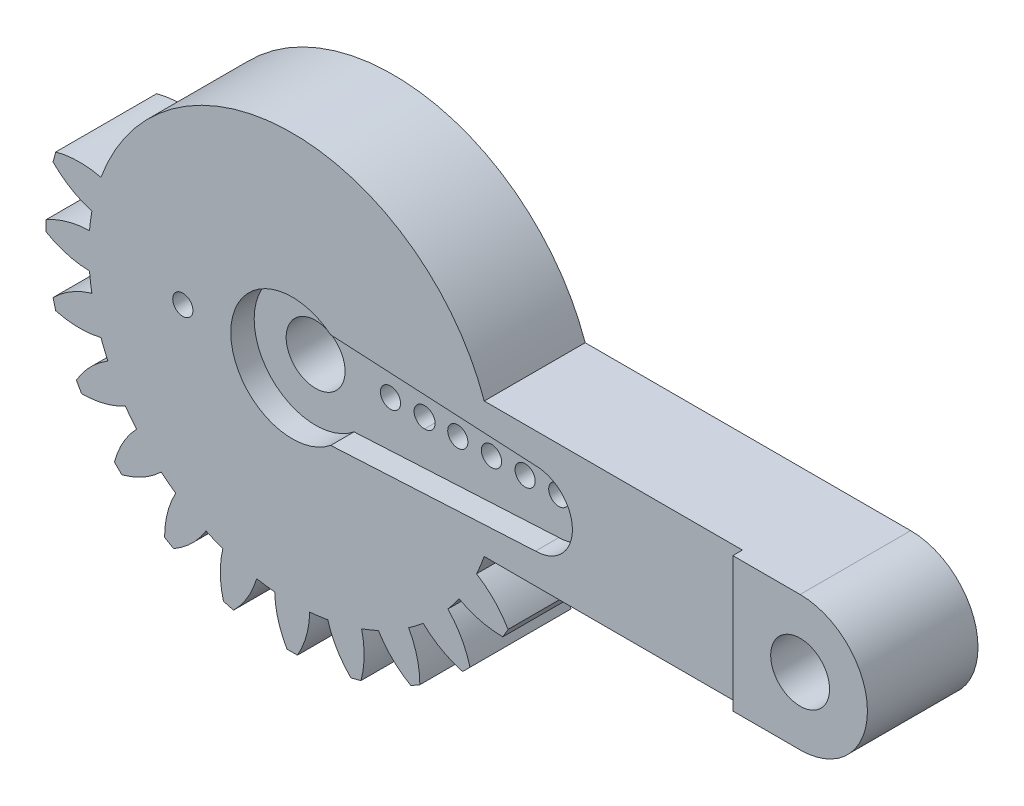
SolidWorks part; units mm, degrees
ref_plane "Front Plane" through (0, 0, 0) normal (0, 0, 1) x (1, 0, 0)
ref_plane "Top Plane" through (0, 0, 0) normal (0, 1, 0) x (1, 0, 0)
ref_plane "Right Plane" through (0, 0, 0) normal (1, 0, 0) x (0, 0, -1)
sketch "Sketch2" plane through (0, 0, 0) normal (0, 0, 1) x (1, 0, 0)
  line L0 (0, 0) -> (30.75, 0) construction
  line L1 (0, -14.63) -> (0, 14.63) construction
  line L2 (-0.31, 14.63) -> (0.31, 14.63)
  line L3 (3.4871, 14.2117) -> (4.086, 14.0513)
  line L4 (7.0465, 12.825) -> (7.5835, 12.515)
  line L5 (10.1258, 10.5642) -> (10.5642, 10.1258)
  line L6 (12.515, 7.5835) -> (12.825, 7.0465)
  line L7 (14.0513, 4.086) -> (14.2117, 3.4871)
  line L8 (14.63, 0.31) -> (14.63, -0.31)
  line L9 (14.2117, -3.4871) -> (14.0513, -4.086)
  line L10 (12.825, -7.0465) -> (12.515, -7.5835)
  line L11 (10.5642, -10.1258) -> (10.1258, -10.5642)
  line L12 (7.5835, -12.515) -> (7.0465, -12.825)
  line L13 (4.086, -14.0513) -> (3.4871, -14.2117)
  line L14 (0.31, -14.63) -> (-0.31, -14.63)
  line L15 (-3.4871, -14.2117) -> (-4.086, -14.0513)
  line L16 (-7.0465, -12.825) -> (-7.5835, -12.515)
  line L17 (-10.1258, -10.5642) -> (-10.5642, -10.1258)
  line L18 (-12.515, -7.5835) -> (-12.825, -7.0465)
  line L19 (-14.0513, -4.086) -> (-14.2117, -3.4871)
  line L20 (-14.63, -0.31) -> (-14.63, 0.31)
  line L21 (-14.2117, 3.4871) -> (-14.0513, 4.086)
  line L22 (-12.825, 7.0465) -> (-12.515, 7.5835)
  line L23 (-10.5642, 10.1258) -> (-10.1258, 10.5642)
  line L24 (-7.5835, 12.515) -> (-7.0465, 12.825)
  line L25 (-4.086, 14.0513) -> (-3.4871, 14.2117)
  line L26 (30.75, -4) -> (30.75, 4) construction
  line L27 (30.75, 4) -> (11.4091, 4)
  line L28 (30.75, -4) -> (11.4091, -4)
  circle A0 centre (0, 0) radius 1.75
  circle A1 centre (0, 0) radius 12.09
  circle A2 centre (30.75, 0) radius 1.75
  arc A3 (-1.04, 12.0452) -> (-0.31, 14.63) centre (4.3585, 11.9161) cw
  arc A4 (1.04, 12.0452) -> (0.31, 14.63) centre (-4.3585, 11.9161) ccw
  arc A5 (4.1221, 11.3656) -> (4.086, 14.0513) centre (-1.1258, 12.6381) ccw
  arc A6 (2.113, 11.9039) -> (3.4871, 14.2117) centre (7.294, 10.382) cw
  arc A7 (6.9233, 9.9114) -> (7.5835, 12.515) centre (2.1835, 12.4988) ccw
  arc A8 (5.1219, 10.9514) -> (7.0465, 12.825) centre (9.7326, 8.1404) cw
  arc A9 (9.2526, 7.7818) -> (10.5642, 10.1258) centre (5.344, 11.5078) ccw
  arc A10 (7.7818, 9.2526) -> (10.1258, 10.5642) centre (11.5078, 5.344) cw
  arc A11 (10.9514, 5.1219) -> (12.825, 7.0465) centre (8.1404, 9.7326) ccw
  arc A12 (9.9114, 6.9233) -> (12.515, 7.5835) centre (12.4988, 2.1835) cw
  arc A13 (11.9039, 2.113) -> (14.2117, 3.4871) centre (10.382, 7.294) ccw
  arc A14 (11.3656, 4.1221) -> (14.0513, 4.086) centre (12.6381, -1.1258) cw
  arc A15 (12.0452, -1.04) -> (14.63, -0.31) centre (11.9161, 4.3585) ccw
  arc A16 (12.0452, 1.04) -> (14.63, 0.31) centre (11.9161, -4.3585) cw
  arc A17 (11.3656, -4.1221) -> (14.0513, -4.086) centre (12.6381, 1.1258) ccw
  arc A18 (11.9039, -2.113) -> (14.2117, -3.4871) centre (10.382, -7.294) cw
  arc A19 (9.9114, -6.9233) -> (12.515, -7.5835) centre (12.4988, -2.1835) ccw
  arc A20 (10.9514, -5.1219) -> (12.825, -7.0465) centre (8.1404, -9.7326) cw
  arc A21 (7.7818, -9.2526) -> (10.1258, -10.5642) centre (11.5078, -5.344) ccw
  arc A22 (9.2526, -7.7818) -> (10.5642, -10.1258) centre (5.344, -11.5078) cw
  arc A23 (5.1219, -10.9514) -> (7.0465, -12.825) centre (9.7326, -8.1404) ccw
  arc A24 (6.9233, -9.9114) -> (7.5835, -12.515) centre (2.1835, -12.4988) cw
  arc A25 (2.113, -11.9039) -> (3.4871, -14.2117) centre (7.294, -10.382) ccw
  arc A26 (4.1221, -11.3656) -> (4.086, -14.0513) centre (-1.1258, -12.6381) cw
  arc A27 (-1.04, -12.0452) -> (-0.31, -14.63) centre (4.3585, -11.9161) ccw
  arc A28 (1.04, -12.0452) -> (0.31, -14.63) centre (-4.3585, -11.9161) cw
  arc A29 (-4.1221, -11.3656) -> (-4.086, -14.0513) centre (1.1258, -12.6381) ccw
  arc A30 (-2.113, -11.9039) -> (-3.4871, -14.2117) centre (-7.294, -10.382) cw
  arc A31 (-6.9233, -9.9114) -> (-7.5835, -12.515) centre (-2.1835, -12.4988) ccw
  arc A32 (-5.1219, -10.9514) -> (-7.0465, -12.825) centre (-9.7326, -8.1404) cw
  arc A33 (-9.2526, -7.7818) -> (-10.5642, -10.1258) centre (-5.344, -11.5078) ccw
  arc A34 (-7.7818, -9.2526) -> (-10.1258, -10.5642) centre (-11.5078, -5.344) cw
  arc A35 (-10.9514, -5.1219) -> (-12.825, -7.0465) centre (-8.1404, -9.7326) ccw
  arc A36 (-9.9114, -6.9233) -> (-12.515, -7.5835) centre (-12.4988, -2.1835) cw
  arc A37 (-11.9039, -2.113) -> (-14.2117, -3.4871) centre (-10.382, -7.294) ccw
  arc A38 (-11.3656, -4.1221) -> (-14.0513, -4.086) centre (-12.6381, 1.1258) cw
  arc A39 (-12.0452, 1.04) -> (-14.63, 0.31) centre (-11.9161, -4.3585) ccw
  arc A40 (-12.0452, -1.04) -> (-14.63, -0.31) centre (-11.9161, 4.3585) cw
  arc A41 (-11.3656, 4.1221) -> (-14.0513, 4.086) centre (-12.6381, -1.1258) ccw
  arc A42 (-11.9039, 2.113) -> (-14.2117, 3.4871) centre (-10.382, 7.294) cw
  arc A43 (-9.9114, 6.9233) -> (-12.515, 7.5835) centre (-12.4988, 2.1835) ccw
  arc A44 (-10.9514, 5.1219) -> (-12.825, 7.0465) centre (-8.1404, 9.7326) cw
  arc A45 (-7.7818, 9.2526) -> (-10.1258, 10.5642) centre (-11.5078, 5.344) ccw
  arc A46 (-9.2526, 7.7818) -> (-10.5642, 10.1258) centre (-5.344, 11.5078) cw
  arc A47 (-5.1219, 10.9514) -> (-7.0465, 12.825) centre (-9.7326, 8.1404) ccw
  arc A48 (-6.9233, 9.9114) -> (-7.5835, 12.515) centre (-2.1835, 12.4988) cw
  arc A49 (-2.113, 11.9039) -> (-3.4871, 14.2117) centre (-7.294, 10.382) ccw
  arc A50 (-4.1221, 11.3656) -> (-4.086, 14.0513) centre (1.1258, 12.6381) cw
  arc A51 (30.75, -4) -> (30.75, 4) centre (30.75, 0) ccw
  point P9 (0, 0)
  point P156 (0, 0)
  point P158 (30.75, 0)
  dimension "D2" = 3.5
  dimension "D3" = 3.5
  dimension "D4" = 24.18
  dimension "D6" = 5.4
  dimension "D10" = 8
  dimension "D1" = 30.75
  dimension "D5" = 29.26
  dimension "D7" = 0.31
  dimension "D8" = 1.04
  dimension "D9" = 24
extrude "Boss-Extrude1" add sketch "Sketch2" against normal blind 10 contours A1 | L28 A51 L27 L7 A13 A1 A16 L8 A15 A18 L9 A2 | A28 A1 A27 L14 | A30 A1 A29 L15 | A32 A1 A31 L16 | A34 A1 A33 L17 | A36 A1 A35 L18 | A38 A1 A37 L19 | A40 A1 A39 L20 | A42 A1 A41 L21 | A26 A1 A25 L13 | A24 A1 A23 L12 | A22 A1 A21 L11 | A20 A1 A19 L10 | A18 A1 L28 L9 | A16 A1 A15 L8 | A1 A13 L7 L27 region at (0, 11.748, 0) region at (-12.7103, 3.4057, 0) region at (12.7154, 3.2861, 0) region at (-13.1586, 0, 0) region at (23.1147, 0, 0) region at (13.1586, 0, 0) region at (-12.7103, -3.4057, 0) region at (12.7154, -3.2861, 0) region at (-11.3957, -6.5793, 0) region at (-9.3046, -9.3046, 0) region at (11.3957, -6.5793, 0) region at (-6.5793, -11.3957, 0) region at (9.3046, -9.3046, 0) region at (-3.4057, -12.7103, 0) region at (6.5793, -11.3957, 0) region at (0, -13.1586, 0) region at (3.4057, -12.7103, 0)
sketch "Sketch10" plane through (0, 0, -10) normal (0, 0, -1) x (-1, 0, 0)
  line L0 (0, 0) -> (-6.5, 0) construction
  line L1 (-6.5, 0) -> (6.5, 0) construction
  circle A0 centre (6.5, 0) radius 0.6
  circle A1 centre (-6.5, 0) radius 0.6
  circle A3 centre (0, 0) radius 1.75 construction
  circle A4 centre (0, 0) radius 1.75
  circle A5 centre (0, 0) radius 1.25
  dimension "D3" = 1.2
  dimension "D4" = 1.2
  dimension "D5" = 3.5
  dimension "D6" = 2.5
  dimension "D1" = 6.5
  dimension "D2" = 6.5
extrude "Cut-Extrude1" cut sketch "Sketch10" against normal through all contours A1 | A0 region at (-6.5, 0, -10) region at (6.5, 0, -10)
sketch "Sketch12" plane through (0, 0, 0) normal (0, 0, 1) x (1, 0, 0)
  line L1 (26.75, 4) -> (26.75, -4)
  line L2 (30.75, 4) -> (11.4091, 4) construction
  line L3 (30.75, -4) -> (11.4091, -4) construction
  point P7 (30.75, 0)
sketch "Sketch13" plane through (0, 0, 0) normal (0, 0, 1) x (1, 0, 0)
  line L0 (26.75, 4) -> (26.75, -4) construction
  line L1 (26.75, 4) -> (26.75, -4)
  line L14 (30.75, 4) -> (11.4091, 4)
  line L15 (-14.0513, 4.086) -> (-14.2117, 3.4871)
  line L16 (-14.63, 0.31) -> (-14.63, -0.31)
  line L17 (-14.2117, -3.4871) -> (-14.0513, -4.086)
  line L18 (-12.825, -7.0465) -> (-12.515, -7.5835)
  line L19 (-10.5642, -10.1258) -> (-10.1258, -10.5642)
  line L20 (-7.5835, -12.515) -> (-7.0465, -12.825)
  line L21 (-4.086, -14.0513) -> (-3.4871, -14.2117)
  line L22 (-0.31, -14.63) -> (0.31, -14.63)
  line L23 (3.4871, -14.2117) -> (4.086, -14.0513)
  line L24 (7.0465, -12.825) -> (7.5835, -12.515)
  line L25 (10.1258, -10.5642) -> (10.5642, -10.1258)
  line L26 (12.515, -7.5835) -> (12.825, -7.0465)
  line L27 (11.4091, -4) -> (30.75, -4)
  line L28 (30.75, 4) -> (11.4091, 4)
  line L29 (-14.0513, 4.086) -> (-14.2117, 3.4871)
  line L30 (-14.63, 0.31) -> (-14.63, -0.31)
  line L31 (-14.2117, -3.4871) -> (-14.0513, -4.086)
  line L32 (-12.825, -7.0465) -> (-12.515, -7.5835)
  line L33 (-10.5642, -10.1258) -> (-10.1258, -10.5642)
  line L34 (-7.5835, -12.515) -> (-7.0465, -12.825)
  line L35 (-4.086, -14.0513) -> (-3.4871, -14.2117)
  line L36 (-0.31, -14.63) -> (0.31, -14.63)
  line L37 (3.4871, -14.2117) -> (4.086, -14.0513)
  line L38 (7.0465, -12.825) -> (7.5835, -12.515)
  line L39 (10.1258, -10.5642) -> (10.5642, -10.1258)
  line L40 (12.515, -7.5835) -> (12.825, -7.0465)
  line L41 (11.4091, -4) -> (30.75, -4)
  circle A0 centre (30.75, 0) radius 1.75 construction
  circle A1 centre (30.75, 0) radius 1.75
  arc A38 (11.4091, 4) -> (-11.3656, 4.1221) centre (0, 0) ccw
  arc A39 (-11.3656, 4.1221) -> (-14.0513, 4.086) centre (-12.6381, -1.1258) ccw
  arc A40 (-14.2117, 3.4871) -> (-11.9039, 2.113) centre (-10.382, 7.294) ccw
  arc A41 (-11.9039, 2.113) -> (-12.0452, 1.04) centre (0, 0) ccw
  arc A42 (-12.0452, 1.04) -> (-14.63, 0.31) centre (-11.9161, -4.3585) ccw
  arc A43 (-14.63, -0.31) -> (-12.0452, -1.04) centre (-11.9161, 4.3585) ccw
  arc A44 (-12.0452, -1.04) -> (-11.9039, -2.113) centre (0, 0) ccw
  arc A45 (-11.9039, -2.113) -> (-14.2117, -3.4871) centre (-10.382, -7.294) ccw
  arc A46 (-14.0513, -4.086) -> (-11.3656, -4.1221) centre (-12.6381, 1.1258) ccw
  arc A47 (-11.3656, -4.1221) -> (-10.9514, -5.1219) centre (0, 0) ccw
  arc A48 (-10.9514, -5.1219) -> (-12.825, -7.0465) centre (-8.1404, -9.7326) ccw
  arc A49 (-12.515, -7.5835) -> (-9.9114, -6.9233) centre (-12.4988, -2.1835) ccw
  arc A50 (-9.9114, -6.9233) -> (-9.2526, -7.7818) centre (0, 0) ccw
  arc A51 (-9.2526, -7.7818) -> (-10.5642, -10.1258) centre (-5.344, -11.5078) ccw
  arc A52 (-10.1258, -10.5642) -> (-7.7818, -9.2526) centre (-11.5078, -5.344) ccw
  arc A53 (-7.7818, -9.2526) -> (-6.9233, -9.9114) centre (0, 0) ccw
  arc A54 (-6.9233, -9.9114) -> (-7.5835, -12.515) centre (-2.1835, -12.4988) ccw
  arc A55 (-7.0465, -12.825) -> (-5.1219, -10.9514) centre (-9.7326, -8.1404) ccw
  arc A56 (-5.1219, -10.9514) -> (-4.1221, -11.3656) centre (0, 0) ccw
  arc A57 (-4.1221, -11.3656) -> (-4.086, -14.0513) centre (1.1258, -12.6381) ccw
  arc A58 (-3.4871, -14.2117) -> (-2.113, -11.9039) centre (-7.294, -10.382) ccw
  arc A59 (-2.113, -11.9039) -> (-1.04, -12.0452) centre (0, 0) ccw
  arc A60 (-1.04, -12.0452) -> (-0.31, -14.63) centre (4.3585, -11.9161) ccw
  arc A61 (0.31, -14.63) -> (1.04, -12.0452) centre (-4.3585, -11.9161) ccw
  arc A62 (1.04, -12.0452) -> (2.113, -11.9039) centre (0, 0) ccw
  arc A63 (2.113, -11.9039) -> (3.4871, -14.2117) centre (7.294, -10.382) ccw
  arc A64 (4.086, -14.0513) -> (4.1221, -11.3656) centre (-1.1258, -12.6381) ccw
  arc A65 (4.1221, -11.3656) -> (5.1219, -10.9514) centre (0, 0) ccw
  arc A66 (5.1219, -10.9514) -> (7.0465, -12.825) centre (9.7326, -8.1404) ccw
  arc A67 (7.5835, -12.515) -> (6.9233, -9.9114) centre (2.1835, -12.4988) ccw
  arc A68 (6.9233, -9.9114) -> (7.7818, -9.2526) centre (0, 0) ccw
  arc A69 (7.7818, -9.2526) -> (10.1258, -10.5642) centre (11.5078, -5.344) ccw
  arc A70 (10.5642, -10.1258) -> (9.2526, -7.7818) centre (5.344, -11.5078) ccw
  arc A71 (9.2526, -7.7818) -> (9.9114, -6.9233) centre (0, 0) ccw
  arc A72 (9.9114, -6.9233) -> (12.515, -7.5835) centre (12.4988, -2.1835) ccw
  arc A73 (12.825, -7.0465) -> (10.9514, -5.1219) centre (8.1404, -9.7326) ccw
  arc A74 (10.9514, -5.1219) -> (11.4091, -4) centre (0, 0) ccw
  arc A75 (30.75, -4) -> (30.75, 4) centre (30.75, 0) ccw
  arc A76 (11.4091, 4) -> (-11.3656, 4.1221) centre (0, 0) ccw
  arc A77 (-11.3656, 4.1221) -> (-14.0513, 4.086) centre (-12.6381, -1.1258) ccw
  arc A78 (-14.2117, 3.4871) -> (-11.9039, 2.113) centre (-10.382, 7.294) ccw
  arc A79 (-11.9039, 2.113) -> (-12.0452, 1.04) centre (0, 0) ccw
  arc A80 (-12.0452, 1.04) -> (-14.63, 0.31) centre (-11.9161, -4.3585) ccw
  arc A81 (-14.63, -0.31) -> (-12.0452, -1.04) centre (-11.9161, 4.3585) ccw
  arc A82 (-12.0452, -1.04) -> (-11.9039, -2.113) centre (0, 0) ccw
  arc A83 (-11.9039, -2.113) -> (-14.2117, -3.4871) centre (-10.382, -7.294) ccw
  arc A84 (-14.0513, -4.086) -> (-11.3656, -4.1221) centre (-12.6381, 1.1258) ccw
  arc A85 (-11.3656, -4.1221) -> (-10.9514, -5.1219) centre (0, 0) ccw
  arc A86 (-10.9514, -5.1219) -> (-12.825, -7.0465) centre (-8.1404, -9.7326) ccw
  arc A87 (-12.515, -7.5835) -> (-9.9114, -6.9233) centre (-12.4988, -2.1835) ccw
  arc A88 (-9.9114, -6.9233) -> (-9.2526, -7.7818) centre (0, 0) ccw
  arc A89 (-9.2526, -7.7818) -> (-10.5642, -10.1258) centre (-5.344, -11.5078) ccw
  arc A90 (-10.1258, -10.5642) -> (-7.7818, -9.2526) centre (-11.5078, -5.344) ccw
  arc A91 (-7.7818, -9.2526) -> (-6.9233, -9.9114) centre (0, 0) ccw
  arc A92 (-6.9233, -9.9114) -> (-7.5835, -12.515) centre (-2.1835, -12.4988) ccw
  arc A93 (-7.0465, -12.825) -> (-5.1219, -10.9514) centre (-9.7326, -8.1404) ccw
  arc A94 (-5.1219, -10.9514) -> (-4.1221, -11.3656) centre (0, 0) ccw
  arc A95 (-4.1221, -11.3656) -> (-4.086, -14.0513) centre (1.1258, -12.6381) ccw
  arc A96 (-3.4871, -14.2117) -> (-2.113, -11.9039) centre (-7.294, -10.382) ccw
  arc A97 (-2.113, -11.9039) -> (-1.04, -12.0452) centre (0, 0) ccw
  arc A98 (-1.04, -12.0452) -> (-0.31, -14.63) centre (4.3585, -11.9161) ccw
  arc A99 (0.31, -14.63) -> (1.04, -12.0452) centre (-4.3585, -11.9161) ccw
  arc A100 (1.04, -12.0452) -> (2.113, -11.9039) centre (0, 0) ccw
  arc A101 (2.113, -11.9039) -> (3.4871, -14.2117) centre (7.294, -10.382) ccw
  arc A102 (4.086, -14.0513) -> (4.1221, -11.3656) centre (-1.1258, -12.6381) ccw
  arc A103 (4.1221, -11.3656) -> (5.1219, -10.9514) centre (0, 0) ccw
  arc A104 (5.1219, -10.9514) -> (7.0465, -12.825) centre (9.7326, -8.1404) ccw
  arc A105 (7.5835, -12.515) -> (6.9233, -9.9114) centre (2.1835, -12.4988) ccw
  arc A106 (6.9233, -9.9114) -> (7.7818, -9.2526) centre (0, 0) ccw
  arc A107 (7.7818, -9.2526) -> (10.1258, -10.5642) centre (11.5078, -5.344) ccw
  arc A108 (10.5642, -10.1258) -> (9.2526, -7.7818) centre (5.344, -11.5078) ccw
  arc A109 (9.2526, -7.7818) -> (9.9114, -6.9233) centre (0, 0) ccw
  arc A110 (9.9114, -6.9233) -> (12.515, -7.5835) centre (12.4988, -2.1835) ccw
  arc A111 (12.825, -7.0465) -> (10.9514, -5.1219) centre (8.1404, -9.7326) ccw
  arc A112 (10.9514, -5.1219) -> (11.4091, -4) centre (0, 0) ccw
  arc A113 (30.75, -4) -> (30.75, 4) centre (30.75, 0) ccw
  dimension "D1" = 0
sketch "Sketch14" plane through (0, 0, -10) normal (0, 0, -1) x (-1, 0, 0)
  line L14 (-11.4091, 4) -> (-30.75, 4)
  line L15 (-30.75, -4) -> (-11.4091, -4)
  line L16 (-12.825, -7.0465) -> (-12.515, -7.5835)
  line L17 (-10.5642, -10.1258) -> (-10.1258, -10.5642)
  line L18 (-7.5835, -12.515) -> (-7.0465, -12.825)
  line L19 (-4.086, -14.0513) -> (-3.4871, -14.2117)
  line L20 (-0.31, -14.63) -> (0.31, -14.63)
  line L21 (3.4871, -14.2117) -> (4.086, -14.0513)
  line L22 (7.0465, -12.825) -> (7.5835, -12.515)
  line L23 (10.1258, -10.5642) -> (10.5642, -10.1258)
  line L24 (12.515, -7.5835) -> (12.825, -7.0465)
  line L25 (14.0513, -4.086) -> (14.2117, -3.4871)
  line L26 (14.63, -0.31) -> (14.63, 0.31)
  line L27 (14.2117, 3.4871) -> (14.0513, 4.086)
  line L28 (-11.4091, 4) -> (-30.75, 4)
  line L29 (-30.75, -4) -> (-11.4091, -4)
  line L30 (-12.825, -7.0465) -> (-12.515, -7.5835)
  line L31 (-10.5642, -10.1258) -> (-10.1258, -10.5642)
  line L32 (-7.5835, -12.515) -> (-7.0465, -12.825)
  line L33 (-4.086, -14.0513) -> (-3.4871, -14.2117)
  line L34 (-0.31, -14.63) -> (0.31, -14.63)
  line L35 (3.4871, -14.2117) -> (4.086, -14.0513)
  line L36 (7.0465, -12.825) -> (7.5835, -12.515)
  line L37 (10.1258, -10.5642) -> (10.5642, -10.1258)
  line L38 (12.515, -7.5835) -> (12.825, -7.0465)
  line L39 (14.0513, -4.086) -> (14.2117, -3.4871)
  line L40 (14.63, -0.31) -> (14.63, 0.31)
  line L41 (14.2117, 3.4871) -> (14.0513, 4.086)
  arc A38 (-30.75, 4) -> (-30.75, -4) centre (-30.75, 0) ccw
  arc A39 (-11.4091, -4) -> (-10.9514, -5.1219) centre (0, 0) ccw
  arc A40 (-10.9514, -5.1219) -> (-12.825, -7.0465) centre (-8.1404, -9.7326) ccw
  arc A41 (-12.515, -7.5835) -> (-9.9114, -6.9233) centre (-12.4988, -2.1835) ccw
  arc A42 (-9.9114, -6.9233) -> (-9.2526, -7.7818) centre (0, 0) ccw
  arc A43 (-9.2526, -7.7818) -> (-10.5642, -10.1258) centre (-5.344, -11.5078) ccw
  arc A44 (-10.1258, -10.5642) -> (-7.7818, -9.2526) centre (-11.5078, -5.344) ccw
  arc A45 (-7.7818, -9.2526) -> (-6.9233, -9.9114) centre (0, 0) ccw
  arc A46 (-6.9233, -9.9114) -> (-7.5835, -12.515) centre (-2.1835, -12.4988) ccw
  arc A47 (-7.0465, -12.825) -> (-5.1219, -10.9514) centre (-9.7326, -8.1404) ccw
  arc A48 (-5.1219, -10.9514) -> (-4.1221, -11.3656) centre (0, 0) ccw
  arc A49 (-4.1221, -11.3656) -> (-4.086, -14.0513) centre (1.1258, -12.6381) ccw
  arc A50 (-3.4871, -14.2117) -> (-2.113, -11.9039) centre (-7.294, -10.382) ccw
  arc A51 (-2.113, -11.9039) -> (-1.04, -12.0452) centre (0, 0) ccw
  arc A52 (-1.04, -12.0452) -> (-0.31, -14.63) centre (4.3585, -11.9161) ccw
  arc A53 (0.31, -14.63) -> (1.04, -12.0452) centre (-4.3585, -11.9161) ccw
  arc A54 (1.04, -12.0452) -> (2.113, -11.9039) centre (0, 0) ccw
  arc A55 (2.113, -11.9039) -> (3.4871, -14.2117) centre (7.294, -10.382) ccw
  arc A56 (4.086, -14.0513) -> (4.1221, -11.3656) centre (-1.1258, -12.6381) ccw
  arc A57 (4.1221, -11.3656) -> (5.1219, -10.9514) centre (0, 0) ccw
  arc A58 (5.1219, -10.9514) -> (7.0465, -12.825) centre (9.7326, -8.1404) ccw
  arc A59 (7.5835, -12.515) -> (6.9233, -9.9114) centre (2.1835, -12.4988) ccw
  arc A60 (6.9233, -9.9114) -> (7.7818, -9.2526) centre (0, 0) ccw
  arc A61 (7.7818, -9.2526) -> (10.1258, -10.5642) centre (11.5078, -5.344) ccw
  arc A62 (10.5642, -10.1258) -> (9.2526, -7.7818) centre (5.344, -11.5078) ccw
  arc A63 (9.2526, -7.7818) -> (9.9114, -6.9233) centre (0, 0) ccw
  arc A64 (9.9114, -6.9233) -> (12.515, -7.5835) centre (12.4988, -2.1835) ccw
  arc A65 (12.825, -7.0465) -> (10.9514, -5.1219) centre (8.1404, -9.7326) ccw
  arc A66 (10.9514, -5.1219) -> (11.3656, -4.1221) centre (0, 0) ccw
  arc A67 (11.3656, -4.1221) -> (14.0513, -4.086) centre (12.6381, 1.1258) ccw
  arc A68 (14.2117, -3.4871) -> (11.9039, -2.113) centre (10.382, -7.294) ccw
  arc A69 (11.9039, -2.113) -> (12.0452, -1.04) centre (0, 0) ccw
  arc A70 (12.0452, -1.04) -> (14.63, -0.31) centre (11.9161, 4.3585) ccw
  arc A71 (14.63, 0.31) -> (12.0452, 1.04) centre (11.9161, -4.3585) ccw
  arc A72 (12.0452, 1.04) -> (11.9039, 2.113) centre (0, 0) ccw
  arc A73 (11.9039, 2.113) -> (14.2117, 3.4871) centre (10.382, 7.294) ccw
  arc A74 (14.0513, 4.086) -> (11.3656, 4.1221) centre (12.6381, -1.1258) ccw
  arc A75 (11.3656, 4.1221) -> (-11.4091, 4) centre (0, 0) ccw
  arc A76 (-30.75, 4) -> (-30.75, -4) centre (-30.75, 0) ccw
  arc A77 (-11.4091, -4) -> (-10.9514, -5.1219) centre (0, 0) ccw
  arc A78 (-10.9514, -5.1219) -> (-12.825, -7.0465) centre (-8.1404, -9.7326) ccw
  arc A79 (-12.515, -7.5835) -> (-9.9114, -6.9233) centre (-12.4988, -2.1835) ccw
  arc A80 (-9.9114, -6.9233) -> (-9.2526, -7.7818) centre (0, 0) ccw
  arc A81 (-9.2526, -7.7818) -> (-10.5642, -10.1258) centre (-5.344, -11.5078) ccw
  arc A82 (-10.1258, -10.5642) -> (-7.7818, -9.2526) centre (-11.5078, -5.344) ccw
  arc A83 (-7.7818, -9.2526) -> (-6.9233, -9.9114) centre (0, 0) ccw
  arc A84 (-6.9233, -9.9114) -> (-7.5835, -12.515) centre (-2.1835, -12.4988) ccw
  arc A85 (-7.0465, -12.825) -> (-5.1219, -10.9514) centre (-9.7326, -8.1404) ccw
  arc A86 (-5.1219, -10.9514) -> (-4.1221, -11.3656) centre (0, 0) ccw
  arc A87 (-4.1221, -11.3656) -> (-4.086, -14.0513) centre (1.1258, -12.6381) ccw
  arc A88 (-3.4871, -14.2117) -> (-2.113, -11.9039) centre (-7.294, -10.382) ccw
  arc A89 (-2.113, -11.9039) -> (-1.04, -12.0452) centre (0, 0) ccw
  arc A90 (-1.04, -12.0452) -> (-0.31, -14.63) centre (4.3585, -11.9161) ccw
  arc A91 (0.31, -14.63) -> (1.04, -12.0452) centre (-4.3585, -11.9161) ccw
  arc A92 (1.04, -12.0452) -> (2.113, -11.9039) centre (0, 0) ccw
  arc A93 (2.113, -11.9039) -> (3.4871, -14.2117) centre (7.294, -10.382) ccw
  arc A94 (4.086, -14.0513) -> (4.1221, -11.3656) centre (-1.1258, -12.6381) ccw
  arc A95 (4.1221, -11.3656) -> (5.1219, -10.9514) centre (0, 0) ccw
  arc A96 (5.1219, -10.9514) -> (7.0465, -12.825) centre (9.7326, -8.1404) ccw
  arc A97 (7.5835, -12.515) -> (6.9233, -9.9114) centre (2.1835, -12.4988) ccw
  arc A98 (6.9233, -9.9114) -> (7.7818, -9.2526) centre (0, 0) ccw
  arc A99 (7.7818, -9.2526) -> (10.1258, -10.5642) centre (11.5078, -5.344) ccw
  arc A100 (10.5642, -10.1258) -> (9.2526, -7.7818) centre (5.344, -11.5078) ccw
  arc A101 (9.2526, -7.7818) -> (9.9114, -6.9233) centre (0, 0) ccw
  arc A102 (9.9114, -6.9233) -> (12.515, -7.5835) centre (12.4988, -2.1835) ccw
  arc A103 (12.825, -7.0465) -> (10.9514, -5.1219) centre (8.1404, -9.7326) ccw
  arc A104 (10.9514, -5.1219) -> (11.3656, -4.1221) centre (0, 0) ccw
  arc A105 (11.3656, -4.1221) -> (14.0513, -4.086) centre (12.6381, 1.1258) ccw
  arc A106 (14.2117, -3.4871) -> (11.9039, -2.113) centre (10.382, -7.294) ccw
  arc A107 (11.9039, -2.113) -> (12.0452, -1.04) centre (0, 0) ccw
  arc A108 (12.0452, -1.04) -> (14.63, -0.31) centre (11.9161, 4.3585) ccw
  arc A109 (14.63, 0.31) -> (12.0452, 1.04) centre (11.9161, -4.3585) ccw
  arc A110 (12.0452, 1.04) -> (11.9039, 2.113) centre (0, 0) ccw
  arc A111 (11.9039, 2.113) -> (14.2117, 3.4871) centre (10.382, 7.294) ccw
  arc A112 (14.0513, 4.086) -> (11.3656, 4.1221) centre (12.6381, -1.1258) ccw
  arc A113 (11.3656, 4.1221) -> (-11.4091, 4) centre (0, 0) ccw
  dimension "D1" = 0
extrude "Cut-Extrude3" cut sketch "Sketch14" against normal blind 4
sketch "Sketch26" plane through (0, 0, 0) normal (0, 0, 1) x (1, 0, 0)
  line L0 (26.75, 4) -> (26.75, -4)
  line L14 (30.75, 4) -> (11.4091, 4)
  line L15 (-14.0513, 4.086) -> (-14.2117, 3.4871)
  line L16 (-14.63, 0.31) -> (-14.63, -0.31)
  line L17 (-14.2117, -3.4871) -> (-14.0513, -4.086)
  line L18 (-12.825, -7.0465) -> (-12.515, -7.5835)
  line L19 (-10.5642, -10.1258) -> (-10.1258, -10.5642)
  line L20 (-7.5835, -12.515) -> (-7.0465, -12.825)
  line L21 (-4.086, -14.0513) -> (-3.4871, -14.2117)
  line L22 (-0.31, -14.63) -> (0.31, -14.63)
  line L23 (3.4871, -14.2117) -> (4.086, -14.0513)
  line L24 (7.0465, -12.825) -> (7.5835, -12.515)
  line L25 (10.1258, -10.5642) -> (10.5642, -10.1258)
  line L26 (12.515, -7.5835) -> (12.825, -7.0465)
  line L27 (11.4091, -4) -> (30.75, -4)
  line L28 (30.75, 4) -> (26.75, 4)
  line L41 (26.75, -4) -> (30.75, -4)
  arc A38 (11.4091, 4) -> (-11.3656, 4.1221) centre (0, 0) ccw
  arc A39 (-11.3656, 4.1221) -> (-14.0513, 4.086) centre (-12.6381, -1.1258) ccw
  arc A40 (-14.2117, 3.4871) -> (-11.9039, 2.113) centre (-10.382, 7.294) ccw
  arc A41 (-11.9039, 2.113) -> (-12.0452, 1.04) centre (0, 0) ccw
  arc A42 (-12.0452, 1.04) -> (-14.63, 0.31) centre (-11.9161, -4.3585) ccw
  arc A43 (-14.63, -0.31) -> (-12.0452, -1.04) centre (-11.9161, 4.3585) ccw
  arc A44 (-12.0452, -1.04) -> (-11.9039, -2.113) centre (0, 0) ccw
  arc A45 (-11.9039, -2.113) -> (-14.2117, -3.4871) centre (-10.382, -7.294) ccw
  arc A46 (-14.0513, -4.086) -> (-11.3656, -4.1221) centre (-12.6381, 1.1258) ccw
  arc A47 (-11.3656, -4.1221) -> (-10.9514, -5.1219) centre (0, 0) ccw
  arc A48 (-10.9514, -5.1219) -> (-12.825, -7.0465) centre (-8.1404, -9.7326) ccw
  arc A49 (-12.515, -7.5835) -> (-9.9114, -6.9233) centre (-12.4988, -2.1835) ccw
  arc A50 (-9.9114, -6.9233) -> (-9.2526, -7.7818) centre (0, 0) ccw
  arc A51 (-9.2526, -7.7818) -> (-10.5642, -10.1258) centre (-5.344, -11.5078) ccw
  arc A52 (-10.1258, -10.5642) -> (-7.7818, -9.2526) centre (-11.5078, -5.344) ccw
  arc A53 (-7.7818, -9.2526) -> (-6.9233, -9.9114) centre (0, 0) ccw
  arc A54 (-6.9233, -9.9114) -> (-7.5835, -12.515) centre (-2.1835, -12.4988) ccw
  arc A55 (-7.0465, -12.825) -> (-5.1219, -10.9514) centre (-9.7326, -8.1404) ccw
  arc A56 (-5.1219, -10.9514) -> (-4.1221, -11.3656) centre (0, 0) ccw
  arc A57 (-4.1221, -11.3656) -> (-4.086, -14.0513) centre (1.1258, -12.6381) ccw
  arc A58 (-3.4871, -14.2117) -> (-2.113, -11.9039) centre (-7.294, -10.382) ccw
  arc A59 (-2.113, -11.9039) -> (-1.04, -12.0452) centre (0, 0) ccw
  arc A60 (-1.04, -12.0452) -> (-0.31, -14.63) centre (4.3585, -11.9161) ccw
  arc A61 (0.31, -14.63) -> (1.04, -12.0452) centre (-4.3585, -11.9161) ccw
  arc A62 (1.04, -12.0452) -> (2.113, -11.9039) centre (0, 0) ccw
  arc A63 (2.113, -11.9039) -> (3.4871, -14.2117) centre (7.294, -10.382) ccw
  arc A64 (4.086, -14.0513) -> (4.1221, -11.3656) centre (-1.1258, -12.6381) ccw
  arc A65 (4.1221, -11.3656) -> (5.1219, -10.9514) centre (0, 0) ccw
  arc A66 (5.1219, -10.9514) -> (7.0465, -12.825) centre (9.7326, -8.1404) ccw
  arc A67 (7.5835, -12.515) -> (6.9233, -9.9114) centre (2.1835, -12.4988) ccw
  arc A68 (6.9233, -9.9114) -> (7.7818, -9.2526) centre (0, 0) ccw
  arc A69 (7.7818, -9.2526) -> (10.1258, -10.5642) centre (11.5078, -5.344) ccw
  arc A70 (10.5642, -10.1258) -> (9.2526, -7.7818) centre (5.344, -11.5078) ccw
  arc A71 (9.2526, -7.7818) -> (9.9114, -6.9233) centre (0, 0) ccw
  arc A72 (9.9114, -6.9233) -> (12.515, -7.5835) centre (12.4988, -2.1835) ccw
  arc A73 (12.825, -7.0465) -> (10.9514, -5.1219) centre (8.1404, -9.7326) ccw
  arc A74 (10.9514, -5.1219) -> (11.4091, -4) centre (0, 0) ccw
  arc A75 (30.75, -4) -> (30.75, 4) centre (30.75, 0) ccw
  arc A113 (30.75, -4) -> (30.75, 4) centre (30.75, 0) ccw
  dimension "D1" = 0
extrude "Boss-Extrude2" add sketch "Sketch26" along normal blind 0.25 contours L41 A113 L28 L0 region at (30.3766, 0, 0)
extrude "Cut-Extrude11" cut sketch "Sketch13" along normal through all contours A1 region at (30.75, 0, 0)
sketch "Sketch27" plane through (0, 4, 0) normal (0, 1, 0) x (1, 0, 0)
  line L0 (34.75, -0.25) -> (34.75, 6) construction
  line L1 (26.75, -0.25) -> (34.75, -0.25)
  line L2 (26.75, -0.25) -> (26.75, -0.2441)
  line L3 (26.75, -0.2441) -> (34.75, -0.2441)
  line L4 (34.75, -0.25) -> (34.75, -0.2441)
  dimension "D1" = 0.0059
sketch "Sketch28" plane through (0, 0, 0) normal (0, 0, 1) x (1, 0, 0)
  line L0 (0, 0) -> (14.45, 0) construction
  line L1 (0, 0) -> (2.21, 0) construction
  line L2 (2.21, 0) -> (2.21, 2.6492) construction
  line L3 (2.21, 2.6492) -> (2.21, -2.6492) construction
  line L4 (14.45, 2) -> (14.45, -2) construction
  line L5 (2.21, 2.6492) -> (14.45, 2)
  line L6 (2.21, -2.6492) -> (14.45, -2)
  arc A0 (2.21, 2.6492) -> (2.21, -2.6492) centre (0, 0) ccw
  arc A1 (14.45, -2) -> (14.45, 2) centre (14.45, 0) ccw
  circle A2 centre (0, 0) radius 2.3
  circle A3 centre (14.45, 0) radius 0.6
  circle A4 centre (12.45, 0) radius 0.6
  circle A5 centre (10.45, 0) radius 0.6
  circle A6 centre (8.45, 0) radius 0.6
  circle A7 centre (6.45, 0) radius 0.6
  circle A8 centre (4.45, 0) radius 0.6
  dimension "D1" = 6.9
  dimension "D3" = 4
  dimension "D4" = 4.6
  dimension "D6" = 1.2
  dimension "D7" = 6
  dimension "D2" = 14.45
  dimension "D5" = 2.21
extrude "Cut-Extrude12" cut sketch "Sketch28" against normal through all contours A6 | A7 | A8 | A5 | A3 | A4 region at (14.45, 0, 0) region at (12.45, 0, 0) region at (10.45, 0, 0) region at (8.45, 0, 0) region at (6.45, 0, 0) region at (4.45, 0, 0)
sketch "Sketch29" plane through (0, 0, 0) normal (0, 0, 1) x (1, 0, 0)
  line L1 (0, 0) -> (2.21, 0) construction
  line L2 (2.21, 0) -> (2.21, 2.6492) construction
  line L3 (2.21, 2.6492) -> (2.21, -2.6492) construction
  line L6 (2.286, 2.8455) -> (14.4554, 2.2)
  line L7 (2.286, -2.8455) -> (14.4554, -2.2)
  arc A2 (14.4554, -2.2) -> (14.4554, 2.2) centre (14.45, 0) ccw
  arc A3 (2.286, 2.8455) -> (2.286, -2.8455) centre (0, 0) ccw
  point P4 (14.45, 0)
  dimension "D3" = 2.21
extrude "Cut-Extrude14" cut sketch "Sketch29" against normal blind 1.39 contours L6 A3 L7 A2 region at (5.6843, 0, 0)
sketch "Sketch30" plane through (0, 0, 0) normal (0, 0, 1) x (1, 0, 0)
  line L3 (26.75, -4) -> (30.75, -4)
  line L4 (30.75, 4) -> (26.75, 4)
  line L5 (26.75, 4) -> (26.75, -4)
  line L6 (26.75, -4) -> (30.75, -4)
  line L7 (30.75, 4) -> (26.75, 4)
  line L8 (26.75, 4) -> (26.75, -4)
  arc A1 (30.75, -4) -> (30.75, 4) centre (30.75, 0) ccw
  arc A2 (30.75, -4) -> (30.75, 4) centre (30.75, 0) ccw
  dimension "D1" = 0
sketch "Sketch31" plane through (0, 0, 0.25) normal (0, 0, 1) x (1, 0, 0)
  line L3 (26.75, -4) -> (30.75, -4)
  line L4 (30.75, 4) -> (26.75, 4)
  line L5 (26.75, 4) -> (26.75, -4)
  line L6 (26.75, -4) -> (30.75, -4)
  line L7 (30.75, 4) -> (26.75, 4)
  line L8 (26.75, 4) -> (26.75, -4)
  arc A1 (30.75, -4) -> (30.75, 4) centre (30.75, 0) ccw
  arc A2 (30.75, -4) -> (30.75, 4) centre (30.75, 0) ccw
  dimension "D1" = 0
extrude "Boss-Extrude3" add sketch "Sketch31" along normal blind 0.32
sketch "Sketch32" plane through (0, 0, -6) normal (0, 0, -1) x (-1, 0, 0)
  circle A1 centre (-30.75, 0) radius 1.75
  circle A2 centre (-30.75, 0) radius 1.75
  dimension "D1" = 0
extrude "Cut-Extrude18" cut sketch "Sketch32" against normal through all
sketch "Sketch34" plane through (0, 4, 0) normal (0, 1, 0) x (1, 0, 0)
  line L0 (32.75, 6) -> (32.75, -0.57) construction
  line L1 (34.75, 6) -> (30.75, 6) construction
  line L2 (30.75, -0.57) -> (34.75, -0.57) construction
